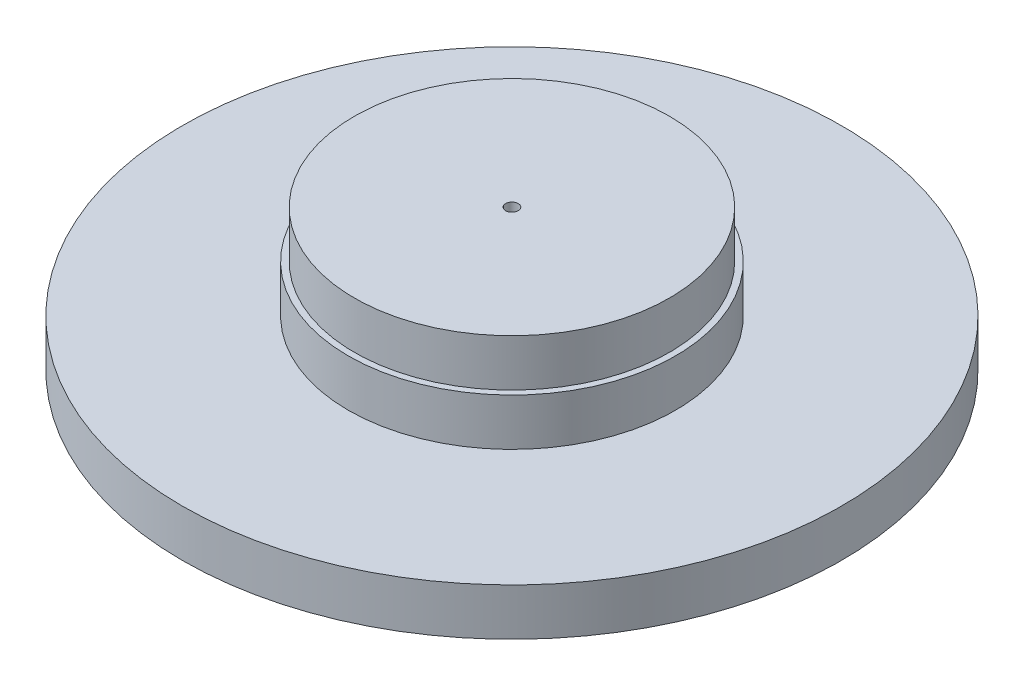
SolidWorks part; units mm, degrees
ref_plane "Front Plane" through (0, 0, 0) normal (0, 0, 1) x (1, 0, 0)
ref_plane "Top Plane" through (0, 0, 0) normal (0, 1, 0) x (1, 0, 0)
ref_plane "Right Plane" through (0, 0, 0) normal (1, 0, 0) x (0, 0, -1)
sketch "Sketch1" plane through (0, 0, 0) normal (0, 1, 0) x (1, 0, 0)
  circle A0 centre (0, 0) radius 84.9884
  circle A1 centre (0, 0) radius 88.265
  circle A2 centre (0, 0) radius 177.8
extrude "Boss-Extrude1" add sketch "Sketch1" along normal blind 76.2 contours A0 region at (0, 0, 0)
extrude "Boss-Extrude2" add sketch "Sketch1<3>" along normal blind 50.8 contours A1 A0 region at (-85.7685, 0, 0)
sketch "Sketch1<3>" plane through (0, 0, 0) normal (0, 1, 0) x (1, 0, 0) same geometry as "Sketch1"
extrude "Boss-Extrude3" add sketch "Sketch1<4>" along normal blind 25.4 contours A2 A1 region at (-172.7711, 0, 0)
sketch "Sketch1<4>" plane through (0, 0, 0) normal (0, 1, 0) x (1, 0, 0) same geometry as "Sketch1"
hole_wizard "CSK for 1/4 Flat Head Machine Screw (100)1" positions "Sketch2" profile "Sketch3" countersink size "1/4" standard "ANSI Inch" end condition through all
sketch "Sketch2" plane through (0, 0, 0) normal (0, -1, 0) x (-1, 0, 0)
  point P0 (0, 0)
sketch "Sketch3" plane through (0, 0, 0) normal (1, 0, 0) x (0, 0, -1)
  line L0 (0, 0) -> (0, 76.2)
  line L1 (0, 76.2) -> (3.3782, 76.2)
  line L2 (3.3782, 76.2) -> (3.3782, 2.5682)
  line L3 (3.3782, 2.5682) -> (6.4389, 0)
  line L5 (6.4389, 0) -> (0, 0)
  line L6 (-3.3782, 2.5682) -> (-6.4389, 0) construction
  line L11 (0, -6.35) -> (0, 107.95) construction
  dimension "Thru Hole Dia." = 6.7564
  dimension "Thru Hole Depth" = 76.2
  dimension "Near C'Sink Dia." = 12.8778
  dimension "Near C'Sink Angle" = 100
